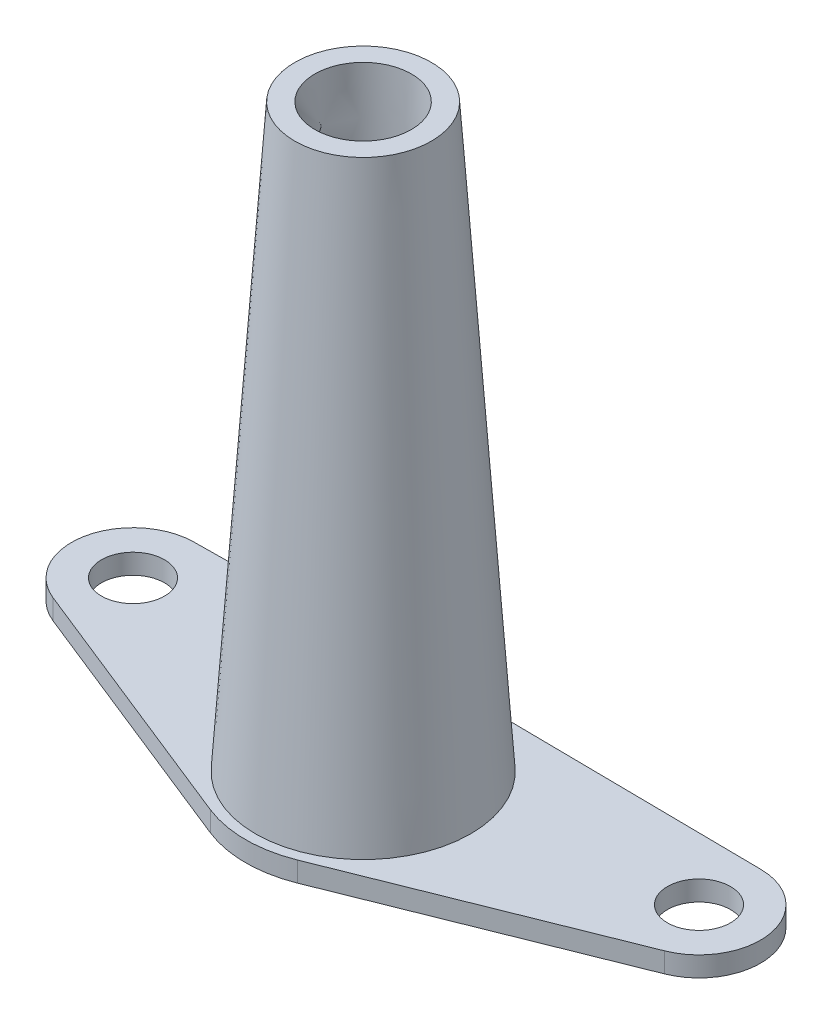
SolidWorks part; units mm, degrees
ref_plane "Front Plane" through (0, 0, 0) normal (0, 0, 1) x (1, 0, 0)
ref_plane "Top Plane" through (0, 0, 0) normal (0, 1, 0) x (1, 0, 0)
ref_plane "Right Plane" through (0, 0, 0) normal (1, 0, 0) x (0, 0, -1)
sketch "Sketch1" plane through (0, 0, 0) normal (0, 1, 0) x (1, 0, 0)
  line L0 (-49.6634, 32.3685) -> (38.7273, -56.0223) construction
  line L1 (-49.6634, 32.3685) -> (38.7273, 32.3685) construction
  line L2 (-49.6634, 32.3685) -> (-49.6634, -56.0223) construction
  line L3 (-49.6634, -56.0223) -> (38.7273, -56.0223) construction
  line L4 (38.7273, 32.3685) -> (38.7273, -56.0223) construction
  line L5 (38.7273, 32.3685) -> (-49.6634, -56.0223) construction
  line L6 (-5.468, -11.8269) -> (-5.468, 20.0481) construction
  line L7 (-36.0367, 10.7474) -> (-9.8326, 0.2637)
  line L8 (-1.1035, 0.2637) -> (25.1006, 10.7474)
  line L9 (-33.821, 22.607) -> (-5.468, 22.9238)
  line L10 (-5.468, 22.9238) -> (22.8849, 22.607)
  circle A0 centre (-33.7523, 16.4573) radius 3.15
  circle A1 centre (-5.468, 11.1731) radius 8.75
  arc A3 (-33.821, 22.607) -> (-36.0367, 10.7474) centre (-33.7523, 16.4573) ccw
  arc A4 (-9.8326, 0.2637) -> (-1.1035, 0.2637) centre (-5.468, 11.1731) ccw
  arc A6 (22.8849, 22.607) -> (25.1006, 10.7474) centre (22.8162, 16.4573) cw
  circle A7 centre (22.8162, 16.4573) radius 3.15
  arc A8 (-5.3367, 22.9223) -> (-5.5993, 22.9223) centre (-5.468, 11.1731) ccw
  circle A9 centre (-33.7523, 16.4573) radius 6.15 construction
  circle A10 centre (-5.468, 11.1731) radius 11.75 construction
  point P8 (-5.468, -11.8269)
  point P19 (-27.871, 18.2554)
  point P21 (5.7685, 14.6084)
  dimension "D1" = 6.3
  dimension "D3" = 17.5
  dimension "D2" = 40
  dimension "D4" = 23
  dimension "D5" = 3
ref_plane "Plane1" through (0, 60, 0) normal (0, 1, 0) x (1, 0, 0)
extrude "Boss-Extrude3" add sketch "Sketch1" along normal blind 2 contours L10 A8 L9 A3 L7 A4 L8 A6 A0 A1 A7 region at (-39.0824, 0, -17.4531)
sketch "Sketch3" plane through (0, 60, 0) normal (0, 1, 0) x (1, 0, 0)
  line L0 (-5.468, 2.4231) -> (-5.468, 19.9231) construction
  circle A2 centre (-5.468, 11.1731) radius 6.8237
  circle A4 centre (-5.468, 11.1731) radius 8.75 construction
sketch "Sketch5" plane through (0, 2, 0) normal (0, 1, 0) x (1, 0, 0)
  circle A2 centre (-5.468, 11.1731) radius 10.75
  circle A3 centre (-5.468, 11.1731) radius 10.75
  dimension "D1" = 2
loft "Loft2" add profiles "Sketch3", "Sketch5" connector at (-5.4938, 60, -4.3494) connector at (-5.468, 2, -0.4231)
sketch "Sketch7" plane through (0, 2, 0) normal (0, 1, 0) x (1, 0, 0)
  circle A6 centre (-5.468, 11.1731) radius 8.75
  circle A7 centre (-5.468, 11.1731) radius 8.75
  dimension "D1" = 0
sketch "Sketch8" plane through (0, 60, 0) normal (0, 1, 0) x (1, 0, 0)
  circle A2 centre (-5.468, 11.1731) radius 4.8237
  circle A3 centre (-5.468, 11.1731) radius 4.8237
  dimension "D1" = 2
loft "Cut-Loft1" cut profiles "Sketch8", "Sketch7" connector at (-4.9812, 60, -6.374) connector at (-11.9964, 2, -5.347)
